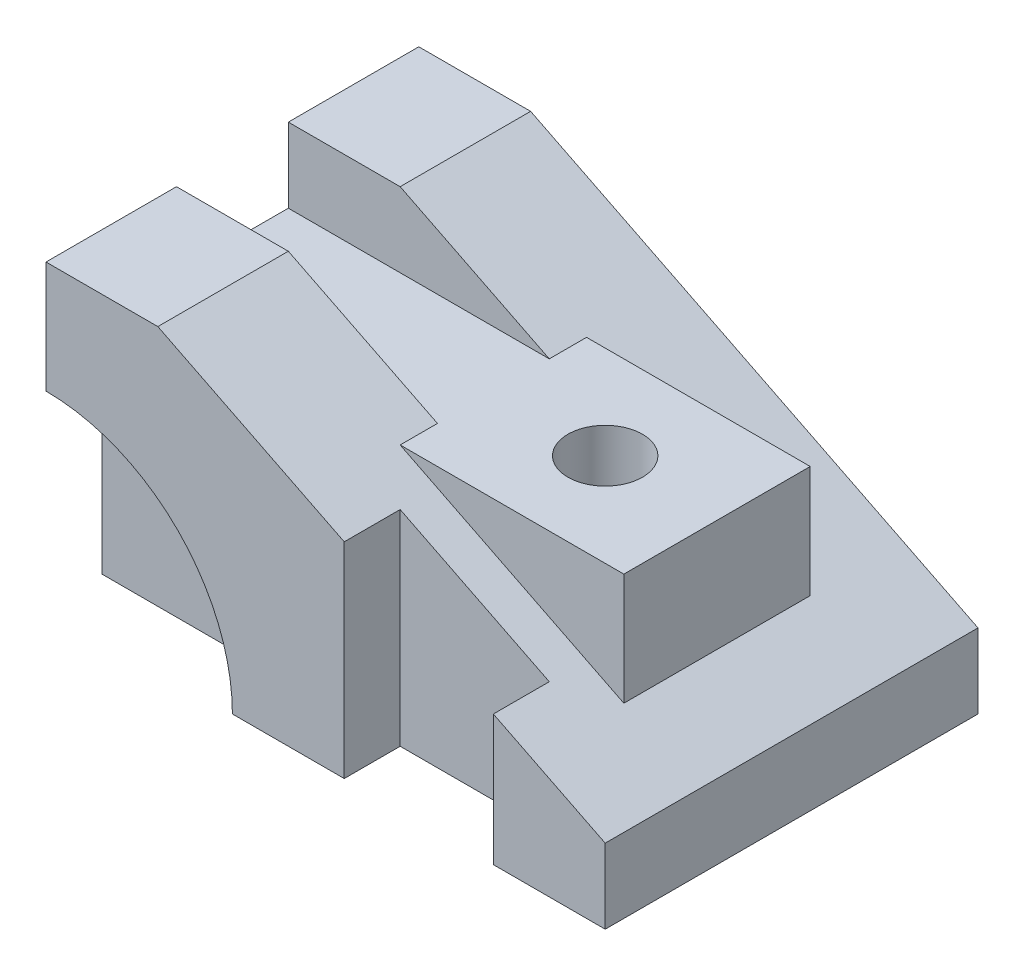
SolidWorks part; units mm, degrees
ref_plane "Front Plane" through (0, 0, 0) normal (0, 0, 1) x (1, 0, 0)
ref_plane "Top Plane" through (0, 0, 0) normal (0, 1, 0) x (1, 0, 0)
ref_plane "Right Plane" through (0, 0, 0) normal (1, 0, 0) x (0, 0, -1)
sketch "Sketch1" plane through (0, 0, 0) normal (0, 0, 1) x (1, 0, 0)
  line L0 (0, 0) -> (150, 0)
  line L1 (150, 0) -> (150, 20)
  line L2 (150, 20) -> (30, 80)
  line L3 (30, 80) -> (0, 80)
  line L4 (0, 80) -> (0, 0)
  dimension "D1" = 150
  dimension "D2" = 20
  dimension "D3" = 80
  dimension "D4" = 30
extrude "Boss-Extrude1" add sketch "Sketch1" against normal blind 50 and the other way blind 50
sketch "Sketch2" plane through (0, 0, 50) normal (0, 0, 1) x (1, 0, 0)
  circle A0 centre (0, 0) radius 50
  dimension "D1" = 100
extrude "Cut-Extrude1" cut sketch "Sketch2" against normal blind 15
sketch "Sketch5" plane through (0, 0, 0) normal (0, 0, 1) x (1, 0, 0)
  line L0 (70, 60) -> (130, 60)
  line L2 (150, 20) -> (30, 80) construction
  line L3 (130, 60) -> (130, 30)
  line L4 (130, 30) -> (70, 60)
  line L5 (150, 0) -> (150, 20) construction
  dimension "D1" = 20
  dimension "D2" = 30
extrude "Boss-Extrude2" add sketch "Sketch5" along normal blind 25 and the other way blind 25
sketch "Sketch6" plane through (0, 60, 0) normal (0, 1, 0) x (1, 0, 0)
  line L1 (-18.4772, 15) -> (116.4118, 15)
  line L2 (-18.4772, 15) -> (-18.4772, -15)
  line L3 (-18.4772, -15) -> (116.4118, -15)
  line L4 (116.4118, 15) -> (116.4118, -15)
  line L7 (150, 50) -> (30, 50) construction
  line L8 (150, -50) -> (30, -50) construction
  dimension "D1" = 35
  dimension "D2" = 35
extrude "Cut-Extrude2" cut sketch "Sketch6" along normal through all
sketch "Sketch7" plane through (0, 60, 0) normal (0, 1, 0) x (1, 0, 0)
  line L0 (0, 0) -> (150, 0) construction
  line L1 (130, 25) -> (130, -25) construction
  circle A0 centre (100, 0) radius 10
  dimension "D2" = 20
  dimension "D1" = 30
extrude "Cut-Extrude3" cut sketch "Sketch7" against normal through all
sketch "Sketch8" plane through (0, 0, 0) normal (0, -1, 0) x (1, 0, 0)
  line L0 (50, 50) -> (150, 50) construction
  line L1 (80, 50) -> (120, 50)
  line L2 (80, 50) -> (80, 35)
  line L3 (80, 35) -> (120, 35)
  line L4 (120, 50) -> (120, 35)
  line L5 (150, 50) -> (150, -50) construction
  dimension "D1" = 30
  dimension "D2" = 40
  dimension "D3" = 15
extrude "Cut-Extrude4" cut sketch "Sketch8" against normal through all
